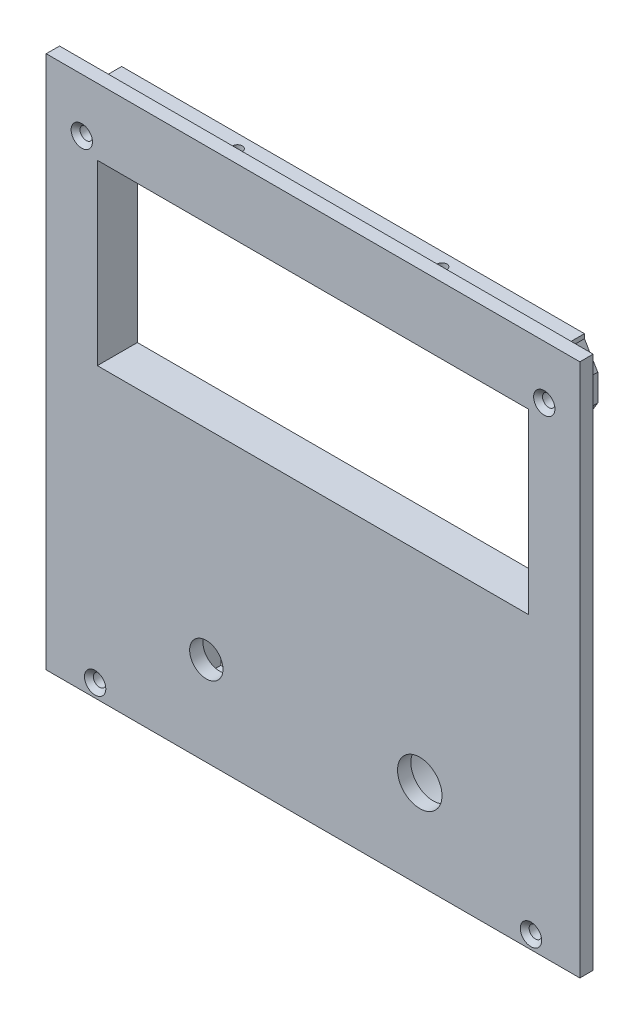
SolidWorks part; units mm, degrees
ref_plane "Płaszczyzna przednia" through (0, 0, 0) normal (0, 0, 1) x (1, 0, 0)
ref_plane "Płaszczyzna górna" through (0, 0, 0) normal (0, 1, 0) x (1, 0, 0)
ref_plane "Płaszczyzna prawa" through (0, 0, 0) normal (1, 0, 0) x (0, 0, -1)
sketch "Szkic1" plane through (0, 0, 0) normal (0, 0, 1) x (1, 0, 0)
  line L0 (60, 88.4954) -> (60, -88.4954) construction
  line L1 (11.5, 65) -> (108.5, 65)
  line L2 (11.5, 65) -> (11.5, 105)
  line L3 (11.5, 105) -> (108.5, 105)
  line L4 (108.5, 65) -> (108.5, 105)
  line L5 (27.4, 40) -> (44.6, 40)
  line L6 (27.4, 40) -> (27.4, 8)
  line L7 (27.4, 8) -> (44.6, 8)
  line L8 (44.6, 40) -> (44.6, 8)
  line L9 (42.25, 23.75) -> (49.1498, 23.75) construction
  line L10 (0, 120) -> (120, 120)
  line L11 (0, 120) -> (0, 0)
  line L12 (0, 0) -> (120, 0)
  line L13 (120, 120) -> (120, 0)
  line L15 (29.75, 26) -> (29.75, 11)
  line L16 (29.75, 11) -> (42.25, 11)
  line L17 (42.25, 26) -> (42.25, 11)
  line L18 (84, -24.1278) -> (84, -84.297) construction
  line L19 (36, 1.7041) -> (36, 61.4933) construction
  line L20 (10.3, 115) -> (10.3, 116.2)
  line L21 (11.5, 115) -> (108.5, 115)
  line L22 (10.3, 116.2) -> (109.7, 116.2)
  line L23 (109.7, 116.2) -> (109.7, 115)
  line L24 (108.5, 55) -> (11.5, 55)
  line L25 (10.3, 55) -> (10.3, 53.8)
  line L26 (36, 20) -> (84, 20) construction
  line L27 (108.5, 55) -> (109.7, 55)
  line L28 (109.7, 55) -> (109.7, 115)
  line L29 (109.7, 115) -> (108.5, 115)
  line L30 (11.5, 115) -> (10.3, 115)
  line L31 (10.3, 115) -> (10.3, 55)
  line L32 (10.3, 55) -> (11.5, 55)
  line L33 (10.3, 53.8) -> (109.7, 53.8)
  line L34 (109.7, 53.8) -> (109.7, 55)
  line L35 (42.25, 26) -> (42.25, 29)
  line L36 (42.25, 29) -> (29.75, 29)
  line L37 (29.75, 29) -> (29.75, 26)
  circle A0 centre (84, 20) radius 11.25
  circle A1 centre (84, 20) radius 13.25
  circle A2 centre (36, 20) radius 3.75
  circle A3 centre (84, 20) radius 5
  point P34 (36, 40)
  dimension "D4" = 22.5
  dimension "D12" = 7.5
  dimension "D19" = 26.5
  dimension "D24" = 10
  dimension "D1" = 97
  dimension "D2" = 40
  dimension "D3" = 17.2
  dimension "D5" = 120
  dimension "D6" = 12.5
  dimension "D7" = 120
  dimension "D8" = 60
  dimension "D9" = 10
  dimension "D10" = 5
  dimension "D11" = 24.5
  dimension "D13" = 15
  dimension "D14" = 12
  dimension "D15" = 3
  dimension "D16" = 15
  dimension "D17" = 24.5
  dimension "D18" = 32
  dimension "D20" = 1.2
  dimension "D21" = 1.2
  dimension "D22" = 1.2
  dimension "D23" = 1.2
  dimension "D25" = 3
extrude "Dodanie-wyciągnięcie1" add sketch "Szkic1" along normal blind 3 contours L31 L32 L24 L27 L28 L29 L21 L30 L4 L1 L2 L3 | L13 L10 L11 L12 A1 L32 L31 L30 L21 L29 L28 L27 L24 L5 L8 L7 L6 | L8 L5 L6 L7 L17 L16 L15 | L17 L15 L16 A2 | A1 A0 | L30 L21 L29 L23 L22 L20 | L33 L34 L27 L24 L32 L25 | A0 A3 region at (36, 39.6367, 0) region at (59.9961, 44.0479, 0) region at (29.9691, 27.5, 0) region at (60, 115.6, 0) region at (10.9, 113.839, 0) region at (60, 54.4, 0) region at (73.0682, 20, 0) region at (71.1248, 20, 0)
extrude "Dodanie-wyciągnięcie3" add sketch "Szkic1<4>" against normal blind 6.5 separate body contours L8 L5 L6 L7 L17 L16 L15 region at (36, 39.6367, 0)
sketch "Szkic1<4>" plane through (0, 0, 0) normal (0, 0, 1) x (1, 0, 0) same geometry as "Szkic1"
extrude "Dodanie-wyciągnięcie4" add sketch "Szkic1<7>" against normal blind 7 contours L21 L3 | L24 L1 | L30 L21 L29 L23 L22 L20 | L33 L34 L27 L24 L32 L25 region at (60, 115.6, 0) region at (10.9, 113.839, 0) region at (60, 54.4, 0)
sketch "Szkic1<7>" plane through (0, 0, 0) normal (0, 0, 1) x (1, 0, 0) same geometry as "Szkic1"
sketch "Szkic7" plane through (0, 0, 3) normal (0, 0, 1) x (1, 0, 0)
  line L0 (5, 111) -> (11, 111)
  line L1 (5, 105) -> (11, 105)
  line L2 (11, 105) -> (11, 111)
  line L3 (5, 111) -> (11, 111)
  line L4 (5, 111) -> (5, 105)
  line L9 (0, 0) -> (120, 0) construction
  line L25 (115, 111) -> (115, 105)
  line L26 (115, 105) -> (109, 105)
  line L28 (109, 105) -> (109, 111)
  line L31 (8, 6) -> (14, 6)
  line L32 (8, 0) -> (14, 0)
  line L33 (14, 0) -> (14, 6)
  line L35 (8, 6) -> (14, 6)
  line L36 (8, 6) -> (8, 0)
  line L37 (112, 6) -> (112, 0)
  line L38 (112, 0) -> (106, 0)
  line L39 (106, 0) -> (106, 6)
  line L40 (112, 6) -> (106, 6)
  line L41 (115, 111) -> (109, 111)
  line L45 (60, 226.7823) -> (60, -90.5786) construction
  line L52 (5, 105) -> (8, 99.9895)
  line L53 (5, 111) -> (8, 116.0105)
  line L54 (115, 111) -> (112, 116.0105)
  line L55 (115, 105) -> (112, 99.9895)
  circle A8 centre (11, 3) radius 1.4
  circle A9 centre (109, 3) radius 1.4
  circle A14 centre (8, 108) radius 1.4
  circle A15 centre (112, 108) radius 1.4
  point P3 (60, 0)
  point P7 (106, 3)
  point P16 (109, 6)
  dimension "D5" = 99
  dimension "D9" = 2.8
  dimension "D2" = 49
  dimension "D7" = 2.8
  dimension "D6" = 2.8
  dimension "D15" = 2.8
  dimension "D17" = 6
  dimension "D3" = 104
  dimension "D4" = 104
  dimension "D8" = 3
  dimension "D10" = 3
  dimension "D11" = 3
  dimension "D12" = 99
  dimension "D13" = 3
  dimension "D14" = 3
  dimension "D16" = 92
  dimension "D18" = 5.84
  dimension "D19" = 6
sketch "Szkic9" plane through (0, 0, -7) normal (0, 0, -1) x (-1, 0, 0)
  line L1 (-60.5, 115) -> (-20.5, 115)
  line L2 (-60.5, 115) -> (-60.5, 111)
  line L3 (-60.5, 111) -> (-20.5, 111)
  line L4 (-20.5, 115) -> (-20.5, 111)
  line L6 (-11.5, 65) -> (-11.5, 105) construction
  line L7 (-11.5, 65) -> (-11.5, 105) construction
  line L8 (-10.3, 116.2) -> (-109.7, 116.2) construction
  dimension "D1" = 40
  dimension "D2" = 4
  dimension "D3" = 9
  dimension "D4" = 1.2
extrude "Wytnij-wyciągnięcie10" cut sketch "Szkic9" against normal blind 1
extrude "Wytnij-wyciągnięcie11" cut sketch "Szkic7" against normal blind 10 contours A9 | A14 | A8 | A15 region at (109, 3, 3) region at (8, 108, 3)
extrude "Dodanie-wyciągnięcie5" add sketch "Szkic1<8>" against normal blind 19 contours A1 A0 region at (71.1248, 20, 0)
sketch "Szkic1<8>" plane through (0, 0, 0) normal (0, 0, 1) x (1, 0, 0) same geometry as "Szkic1"
sketch "Szkic11" plane through (0, 0, -6.5) normal (0, 0, -1) x (-1, 0, 0)
  line L0 (-27.4, 37) -> (-44.6, 37)
  line L4 (-44.6, 40) -> (-44.6, 8)
  line L5 (-44.6, 8) -> (-27.4, 8)
  line L6 (-27.4, 8) -> (-27.4, 40)
  line L7 (-27.4, 40) -> (-44.6, 40)
  line L8 (-44.6, 40) -> (-44.6, 8)
  line L9 (-44.6, 8) -> (-27.4, 8)
  line L10 (-27.4, 8) -> (-27.4, 40)
  line L11 (-27.4, 40) -> (-44.6, 40)
  line M7 (-44.6, 40) -> (-44.6, 8)
  line M9 (-27.4, 8) -> (-27.4, 40)
  line M10 (-27.4, 40) -> (-44.6, 40)
  dimension "D2" = 3
  dimension "D1" = 0
extrude "Wytnij-wyciągnięcie13" cut sketch "Szkic11" against normal blind 4 contours L0 M9 M10 M7 region at (36, 38.5, -6.5)
ref_plane "Płaszczyzna1" through (0, 33.25, 0) normal (0, 1, 0) x (1, 0, 0)
sketch "Szkic12" plane through (0, 33.25, 0) normal (0, 1, 0) x (1, 0, 0)
  line L0 (97.25, 0) -> (70.75, 0) construction
  line L1 (78, 19) -> (90, 19)
  line L2 (78, 19) -> (78, 0)
  line L3 (78, 0) -> (90, 0)
  line L4 (90, 19) -> (90, 0)
  line L9 (70.75, 19) -> (97.25, 19)
  line L10 (84, 19) -> (84, 0.6021) construction
  dimension "D1" = 12
extrude "Wytnij-wyciągnięcie14" cut sketch "Szkic12" against normal blind 4 contours L10 L1 L2 L3 | L9 L10 L3 L4 region at (84, 33.25, -9.5)
sketch "Szkic13" plane through (0, 0, -7) normal (0, 0, -1) x (-1, 0, 0)
  line L0 (-108.5, 65) -> (-108.5, 105) construction
  line L1 (-10.3, 55) -> (-11.5, 55) construction
  line L2 (-108.5, 55) -> (-11.5, 55) construction
  line L3 (-108.5, 55) -> (-109.7, 55) construction
  line L4 (-109.7, 55) -> (-109.7, 115) construction
  line L5 (0, 120) -> (-120, 120)
  line L6 (-120, 120) -> (-120, 0)
  line L7 (-120, 0) -> (0, 0)
  line L8 (0, 0) -> (0, 120)
  line L9 (0, 120) -> (-120, 120)
  line L10 (-120, 120) -> (-120, 0)
  line L11 (-120, 0) -> (0, 0)
  line L12 (0, 0) -> (0, 120)
  line L13 (-27.4, 40) -> (-44.6, 40)
  line L14 (-44.6, 40) -> (-44.6, 8)
  line L15 (-44.6, 8) -> (-27.4, 8)
  line L16 (-27.4, 8) -> (-27.4, 40)
  line L17 (-27.4, 40) -> (-44.6, 40)
  line L18 (-44.6, 40) -> (-44.6, 8)
  line L19 (-44.6, 8) -> (-27.4, 8)
  line L20 (-27.4, 8) -> (-27.4, 40)
  line L21 (-108.5, 65) -> (-11.5, 65)
  line L22 (-108.5, 105) -> (-108.5, 65)
  line L23 (-11.5, 105) -> (-108.5, 105)
  line L24 (-11.5, 65) -> (-11.5, 105)
  line L25 (-108.5, 65) -> (-11.5, 65)
  line L26 (-108.5, 105) -> (-108.5, 65)
  line L27 (-11.5, 105) -> (-108.5, 105)
  line L28 (-11.5, 65) -> (-11.5, 105)
  line L29 (-42.25, 26) -> (-42.25, 11)
  line L37 (-10.3, 55) -> (-10.3, 53.8) construction
  line L38 (-10.3, 53.8) -> (-109.7, 53.8) construction
  line L39 (-109.7, 53.8) -> (-109.7, 55) construction
  line L40 (-10.3, 115) -> (-10.3, 55) construction
  line L41 (-10.3, 115) -> (-10.3, 116.2) construction
  line L42 (-10.3, 116.2) -> (-109.7, 116.2) construction
  line L43 (-109.7, 116.2) -> (-109.7, 115) construction
  line L44 (-109.7, 115) -> (-108.5, 115) construction
  line L45 (-11.5, 115) -> (-108.5, 115) construction
  line L46 (-11.5, 115) -> (-10.3, 115) construction
  line L47 (-10.3, 55) -> (-11.5, 55)
  line L48 (-108.5, 55) -> (-11.5, 55)
  line L49 (-108.5, 55) -> (-109.7, 55)
  line L50 (-109.7, 55) -> (-109.7, 115)
  line L51 (-10.3, 55) -> (-10.3, 53.8)
  line L52 (-10.3, 53.8) -> (-109.7, 53.8)
  line L53 (-109.7, 53.8) -> (-109.7, 55)
  line L54 (-10.3, 115) -> (-10.3, 55)
  line L55 (-10.3, 115) -> (-10.3, 116.2)
  line L56 (-10.3, 116.2) -> (-109.7, 116.2)
  line L57 (-109.7, 116.2) -> (-109.7, 115)
  line L58 (-109.7, 115) -> (-108.5, 115)
  line L59 (-11.5, 115) -> (-108.5, 115)
  line L60 (-11.5, 115) -> (-10.3, 115)
  line L61 (-60, 116.2) -> (-60, 53.8) construction
  line L62 (-109.7, 85) -> (-10.3, 85) construction
  line L66 (-42.25, 26) -> (-42.25, 11)
  line L67 (-42.25, 11) -> (-29.75, 11)
  line L68 (-42.25, 11) -> (-29.75, 11)
  line L69 (-29.75, 11) -> (-29.75, 26)
  line L70 (-29.75, 11) -> (-29.75, 26)
  line L71 (-29.75, 26) -> (-29.75, 29)
  line L72 (-29.75, 26) -> (-29.75, 29)
  line L73 (-29.75, 29) -> (-42.25, 29)
  line L74 (-29.75, 29) -> (-42.25, 29)
  line L75 (-42.25, 29) -> (-42.25, 26)
  line L76 (-42.25, 29) -> (-42.25, 26)
  circle A0 centre (-106.5, 113) radius 2
  circle A1 centre (-13.5, 113) radius 2
  circle A2 centre (-84, 20) radius 11.25
  circle A3 centre (-84, 20) radius 11.25
  circle A4 centre (-36, 20) radius 3.75
  circle A5 centre (-36, 20) radius 3.75
  circle A6 centre (-84, 20) radius 13.25
  circle A7 centre (-84, 20) radius 13.25
  circle A8 centre (-84, 20) radius 5
  circle A9 centre (-84, 20) radius 5
  circle A10 centre (-13.5, 57) radius 2
  circle A11 centre (-106.5, 57) radius 2
  circle A12 centre (-106.5, 113) radius 1.1
  circle A13 centre (-13.5, 113) radius 1.1
  circle A14 centre (-13.5, 57) radius 1.1
  circle A15 centre (-106.5, 57) radius 1.1
  dimension "D1" = 4
  dimension "D10" = 2.2
  dimension "D11" = 1.2
  dimension "D2" = 0
  dimension "D3" = 0
  dimension "D4" = 0
  dimension "D5" = 0
  dimension "D6" = 0
  dimension "D7" = 0
  dimension "D8" = 0
  dimension "D9" = 0
extrude "Wytnij-wyciągnięcie15" cut sketch "Szkic13" against normal up to surface (7 mm away) contours A12 | A13 | A15 | A14 region at (106.5, 113, -7) region at (13.5, 113, -7) region at (106.5, 57, -7) up to face at (84, 19.2075, 0)
sketch "Szkic14" plane through (0, 116.2, 0) normal (0, 1, 0) x (1, 0, 0)
  line L0 (86, 0) -> (80, 0)
  line L1 (37, 8.3134) -> (37, 0) construction
  line L2 (37, 3) -> (37, 8.3134) construction
  line L3 (40, 6) -> (34, 6)
  line L4 (86, 6) -> (86, 0)
  line L5 (80, 6) -> (80, 0)
  line L6 (83, 3) -> (83, 8.3134) construction
  line L7 (83, 8.3134) -> (83, 0) construction
  line L8 (60, 8.3134) -> (60, 2.3134) construction
  line L9 (80, 6) -> (86, 6)
  line L10 (40, 6) -> (40, 0)
  line L11 (34, 6) -> (34, 0)
  line L12 (34, 0) -> (40, 0)
  line L13 (10.3, 7) -> (109.7, 7) construction
  line L14 (10.3, 7) -> (109.7, 7)
  line L15 (0, 0) -> (120, 0) construction
  circle A0 centre (83, 3) radius 1.1
  circle A1 centre (37, 3) radius 1.1
  point P8 (34, 3)
  point P21 (60, 7)
  line M11 (10.3, 0) -> (109.7, 0)
  dimension "D1" = 2.2
  dimension "D2" = 3
  dimension "D3" = 20
  dimension "D4" = 3
extrude "Dodanie-wyciągnięcie6" add sketch "Szkic14" along normal blind 0.8 contours L3 L11 L10 A1 M11 | L9 L5 L4 A0 M11 region at (37, 116.2, -0.0849) region at (83, 116.2, -0.0849)
sketch "Szkic15" plane through (0, 116.2, 0) normal (0, 1, 0) x (1, 0, 0)
  line L14 (80, 0) -> (80, 6)
  line L16 (109.7, 0) -> (109.7, 7)
  line L17 (109.7, 7) -> (10.3, 7)
  line L28 (109.7, 0) -> (109.7, 7)
  line L29 (109.7, 7) -> (10.3, 7)
  line L68 (86, 6) -> (86, 0)
  line L70 (86, 6) -> (86, 0)
  line L72 (86, 0) -> (109.7, 0)
  line L74 (86, 0) -> (109.7, 0)
  line L78 (80, 0) -> (80, 6)
  line L86 (80, 6) -> (86, 6)
  line L90 (80, 6) -> (86, 6)
  line L94 (10.3, 7) -> (10.3, 0)
  line L96 (10.3, 7) -> (10.3, 0)
  line L98 (10.3, 0) -> (34, 0)
  line L100 (10.3, 0) -> (34, 0)
  line L102 (34, 0) -> (34, 6)
  line L103 (34, 0) -> (34, 6)
  line L104 (34, 6) -> (40, 6)
  line L105 (34, 6) -> (40, 6)
  line L106 (40, 6) -> (40, 0)
  line L107 (40, 6) -> (40, 0)
  line L108 (40, 0) -> (80, 0)
  line L109 (40, 0) -> (80, 0)
  dimension "D1" = 0
extrude "Dodanie-wyciągnięcie7" add sketch "Szkic15" along normal up to surface (0.8 mm away) up to face at (81.9, 117, -3)
chamfer "Sfazowanie1" distance 1 angle 45 1 edges at (9.4, 108, 3)
chamfer "Sfazowanie2" distance 1 angle 45 1 edges at (110.6, 108, 3)
chamfer "Sfazowanie3" distance 1 angle 45 1 edges at (12.4, 3, 3)
chamfer "Sfazowanie4" distance 1 angle 45 1 edges at (110.4, 3, 3)
sketch "Szkic17" plane through (0, 0, 0) normal (0, 0, -1) x (-1, 0, 0)
  line L0 (-106.0325, 3) -> (-106.0325, 6)
  line L1 (-14.0325, 6) -> (-14.0325, 3)
  line L2 (-14.0325, 3) -> (-106.0325, 3)
  line L3 (-7.9675, 0) -> (-7.9675, 99.9895)
  line L4 (-7.9675, 99.9895) -> (-4.9675, 105)
  line L5 (-4.9675, 105) -> (-4.9675, 111)
  line L6 (-4.9675, 111) -> (-7.9675, 116.0105)
  line L7 (-7.9675, 116.0105) -> (-7.9675, 117)
  line L8 (-7.9675, 117) -> (-10.9675, 117)
  line L9 (-10.9675, 117) -> (-10.9675, 6)
  line L10 (-10.9675, 6) -> (-14.0325, 6)
  line L11 (-106.0325, 6) -> (-109.0325, 6)
  line L12 (-109.0325, 6) -> (-109.0325, 117)
  line L13 (-109.0325, 117) -> (-112.0325, 117)
  line L14 (-112.0325, 117) -> (-112.0325, 116.0105)
  line L15 (-112.0325, 116.0105) -> (-115.0325, 111)
  line L16 (-115.0325, 111) -> (-115.0325, 105)
  line L17 (-115.0325, 105) -> (-112.0325, 99.9895)
  line L18 (-112.0325, 99.9895) -> (-112.0325, 0)
  line L19 (-112.0325, 0) -> (-7.9675, 0)
  line L20 (-60, 117) -> (-60, -10.665) construction
  line L21 (-109.7, 117) -> (-10.3, 117) construction
  circle A0 centre (-112, 108) radius 1.4 construction
  circle A1 centre (-112, 108) radius 1.4
  circle A2 centre (-8, 108) radius 1.4 construction
  circle A3 centre (-11, 3) radius 1.4 construction
  circle A4 centre (-109, 3) radius 1.4 construction
  circle A5 centre (-8, 108) radius 1.4
  circle A6 centre (-11, 3) radius 1.4
  circle A7 centre (-109, 3) radius 1.4
  point P33 (-115.0325, 108)
  circle M27 centre (-11, 3) radius 1.4
  line M30 (-120, 0) -> (0, 0)
  circle M33 centre (-109, 3) radius 1.4
  circle M34 centre (-8, 108) radius 1.4
  circle M35 centre (-112, 108) radius 1.4
  line M37 (-109.7, 53.8) -> (-109.7, 117)
  line M39 (-10.3, 117) -> (-10.3, 53.8)
  line M40 (-10.3, 53.8) -> (-109.7, 53.8)
  dimension "D1" = 5.84
  dimension "D2" = 6
  dimension "D3" = 5.84
  dimension "D4" = 99.9895
  dimension "D5" = 111
  dimension "D6" = 3
  dimension "D7" = 149.089
  dimension "D8" = 149.089
  dimension "D9" = 149.089
  dimension "D10" = 149.089
  dimension "D11" = 0.9895
extrude "Dodanie-wyciągnięcie9" add sketch "Szkic17" along normal blind 6 contours L20 L2 L0 L11 L12 L13 L14 L15 L16 L17 L18 M40 M37 M30 M35 M33 | L2 L20 L19 L3 L4 L5 L6 L7 L9 L10 L1 M39 M40 M34 M27 region at (83.0162, 1.707, 0) region at (37.0162, 1.707, 0)
sketch "Szkic18" plane through (0, 0, -7) normal (0, 0, -1) x (-1, 0, 0)
  line L4 (-10.3, 53.8) -> (-10.3, 117)
  line L5 (-10.3, 117) -> (-109.7, 117)
  line L6 (-109.7, 117) -> (-109.7, 53.8)
  line L7 (-109.7, 53.8) -> (-10.3, 53.8)
  line L8 (-10.3, 53.8) -> (-10.3, 117)
  line L9 (-10.3, 117) -> (-109.7, 117)
  line L10 (-109.7, 117) -> (-109.7, 53.8)
  line L11 (-109.7, 53.8) -> (-10.3, 53.8)
  dimension "D1" = 0
extrude "Wytnij-wyciągnięcie16" cut sketch "Szkic18" against normal blind 1
sketch "Szkic19" plane through (0, 117, 0) normal (0, 1, 0) x (1, 0, 0)
  line L4 (112.0325, 0) -> (112.0325, 6)
  line L5 (112.0325, 6) -> (7.9675, 6)
  line L6 (7.9675, 6) -> (7.9675, 0)
  line L7 (7.9675, 0) -> (112.0325, 0)
  line L8 (112.0325, 0) -> (112.0325, 6)
  line L9 (112.0325, 6) -> (7.9675, 6)
  line L10 (7.9675, 6) -> (7.9675, 0)
  line L11 (7.9675, 0) -> (112.0325, 0)
  circle M5 centre (37, 3) radius 1.1
  circle M6 centre (83, 3) radius 1.1
  dimension "D1" = 0
extrude "Wytnij-wyciągnięcie17" cut sketch "Szkic19" against normal blind 5 contours M5 | M6 region at (37, 117, -3) region at (83, 117, -3)
